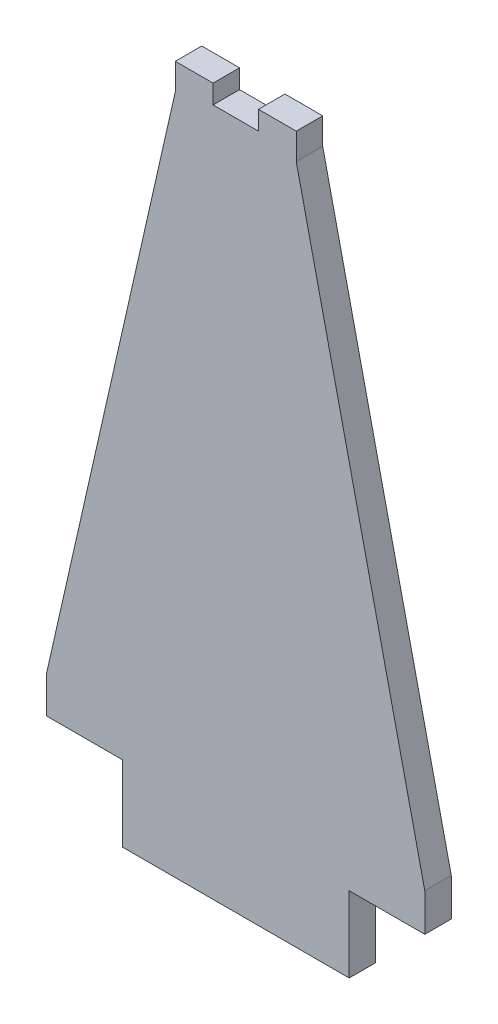
SolidWorks part; units mm, degrees
material "PBT General Purpose"
ref_plane "Front Plane" through (0, 0, 0) normal (0, 0, 1) x (1, 0, 0)
ref_plane "Top Plane" through (0, 0, 0) normal (0, 1, 0) x (1, 0, 0)
ref_plane "Right Plane" through (0, 0, 0) normal (1, 0, 0) x (0, 0, -1)
sketch "frame_outline" plane through (0, 0, 0) normal (0, 0, 1) x (1, 0, 0)
  line L110 (0, 0) -> (3, 0)
  line L117 (3, 0) -> (3, 1)
  line L118 (3, 1) -> (4, 1)
  line L119 (4, 1) -> (4, 1.5)
  line L120 (4, 1.5) -> (2.3, 9)
  line L121 (2.3, 9) -> (2.3, 9.35)
  line L122 (2.3, 9.35) -> (1.8, 9.35)
  line L123 (1.8, 9.35) -> (1.8, 9.1)
  line L124 (1.8, 9.1) -> (1.2, 9.1)
  line L125 (1.2, 9.1) -> (1.2, 9.35)
  line L126 (1.2, 9.35) -> (0.7, 9.35)
  line L127 (0.7, 9.35) -> (0.7, 9)
  line L128 (0.7, 9) -> (-1, 1.5)
  line L129 (-1, 1.5) -> (-1, 1)
  line L130 (-1, 1) -> (0, 1)
  line L131 (0, 1) -> (0, 0)
  line L132 (1.5, 9.1) -> (1.5, 0) construction
  dimension "D1" = 5
  dimension "D2" = 3
  dimension "D3" = 1
  dimension "D4" = 0.5
  dimension "D5" = 8
  dimension "D6" = 0.6
  dimension "D7" = 0.25
  dimension "D8" = 0.5
  dimension "D9" = 0.1
extrude "Boss-Extrude1" add sketch "frame_outline" along normal mid plane 0.35
equation "\"t\"= 0.25'thickness of the sheets"
equation "\"t_cf\" = 0.115'thickness of single carbon fiber layer"
equation "\"t_kapton\" = 0.025'thickness of single Kapton flex layer"
equation "\"t_fr4\" = 0.1'thickness of FR4 with copper layer"
equation "\"joint_flex\"= 0.1'Width of flextures gap"
equation "\"joint_flex_eff\"= 0.02'Width of flecture after castelation"
equation "\"joint_fold\"= 0.2'Width of folding joints for 90deg fold"
equation "\"gap_tolerance\"= 0.002'Width to have interfecence fit between carbon fiber inserts"
equation "\"assemble_angle\"= 90'Angle of assembly parts"
equation "\"D1@Boss-Extrude1\"=0.35"
equation "\"link_lift\"= 0.5'Actuation linkage amplification for the lift motion"
equation "\"link_swing\"= 0.45'Actuation linkage amplification for the swing motion"
